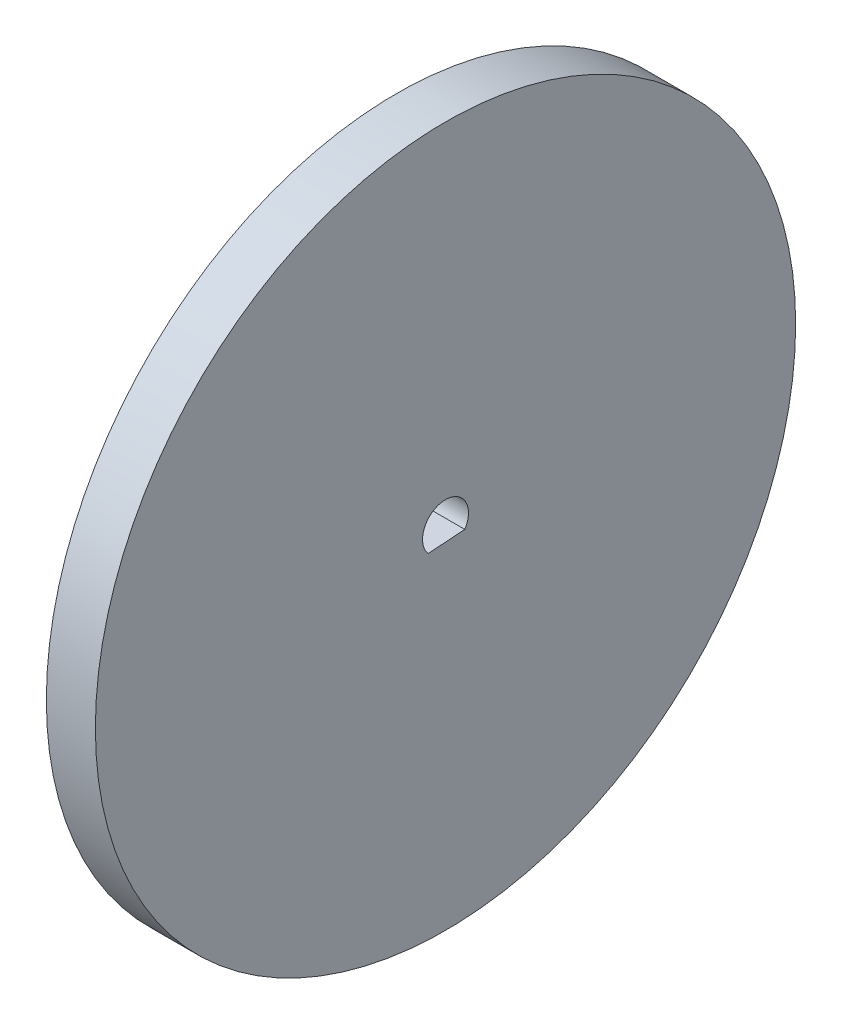
SolidWorks part; units mm, degrees
ref_plane "Front Plane" through (0, 0, 0) normal (0, 0, 1) x (1, 0, 0)
ref_plane "Top Plane" through (0, 0, 0) normal (0, 1, 0) x (1, 0, 0)
ref_plane "Right Plane" through (0, 0, 0) normal (1, 0, 0) x (0, 0, -1)
sketch "Sketch1" plane through (0, 0, 0) normal (1, 0, 0) x (0, 0, -1)
  circle A0 centre (0, 0) radius 38.1
  dimension "D1" = 76.2
extrude "Boss-Extrude1" add sketch "Sketch1" along normal blind 5.334
sketch "Sketch5" plane through (5.334, 0, 0) normal (1, 0, 0) x (0, 0, -1)
  line L0 (-1.8893, -1.6372) -> (2.1007, -1.3553) construction
  line L1 (-1.8893, -1.6372) -> (2.1007, -1.3553)
  arc A0 (2.1007, -1.3553) -> (-1.8893, -1.6372) centre (0, 0) ccw construction
  arc A3 (2.1007, -1.3553) -> (-1.8893, -1.6372) centre (0, 0) ccw
extrude "Cut-Extrude1" cut sketch "Sketch5" against normal through all
equation "\"material\"=\"GMaterial@Platform.assembly\""
equation "\"D1@Boss-Extrude1\"=\"material\""
